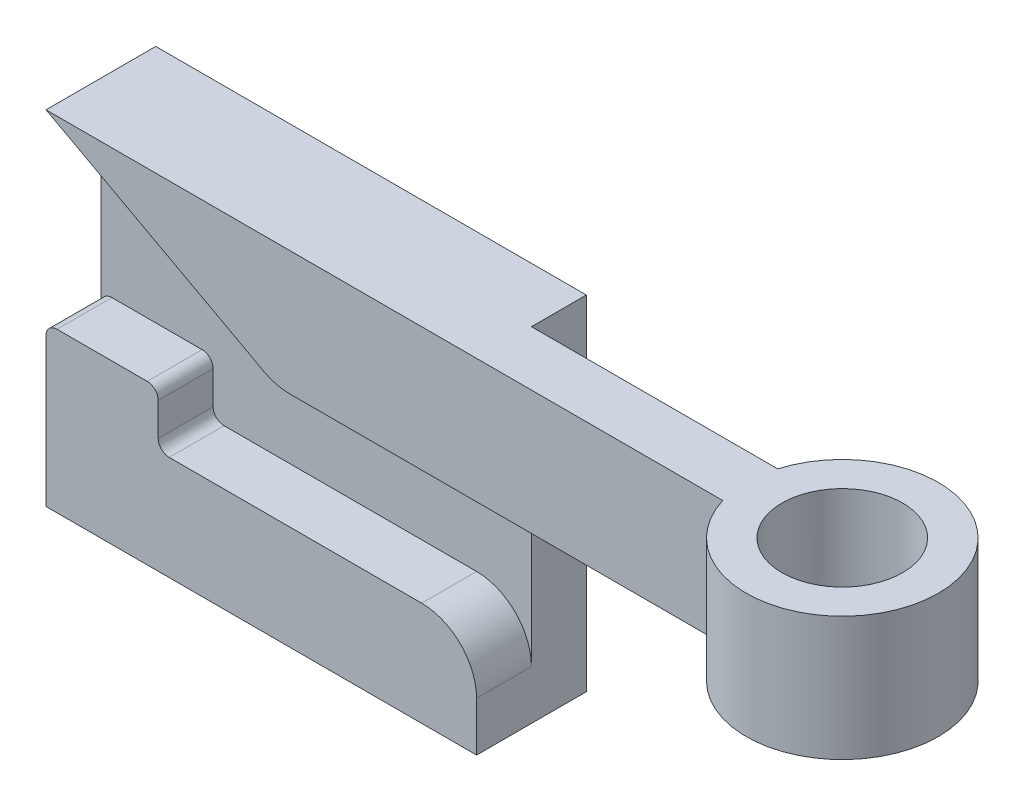
SolidWorks part; units mm, degrees
ref_plane "Front Plane" through (0, 0, 0) normal (0, 0, 1) x (1, 0, 0)
ref_plane "Top Plane" through (0, 0, 0) normal (0, 1, 0) x (1, 0, 0)
ref_plane "Right Plane" through (0, 0, 0) normal (1, 0, 0) x (0, 0, -1)
sketch "Sketch1" plane through (0, 0, 0) normal (0, 0, 1) x (1, 0, 0)
  line L1 (123.321, 27.8206) -> (41.9062, 27.8206)
  line L2 (41.9062, 27.8206) -> (0, 50.4466)
  line L3 (20.4481, 6.8206) -> (78.4559, 6.8206)
  line L6 (0, 16.8206) -> (20.4481, 16.8206)
  line L7 (20.4481, 6.8206) -> (20.4481, 16.8206)
  line L10 (0, 0) -> (0, -12.1545)
  line L11 (0, -12.1545) -> (78.4559, -12.1545)
  line L12 (78.4559, -12.1545) -> (78.4559, 6.8206)
  line L13 (0, 0) -> (0, 16.8206)
  line L14 (0, 50.4466) -> (123.321, 50.4466)
  line L17 (123.321, 50.4466) -> (123.321, 27.8206)
  point P3 (0, 67.3903)
  point P4 (50.4529, 26.6662)
  point P11 (0, 10.2755)
  point P14 (41.9062, 27.8206)
  point P16 (0, 50.4466)
  dimension "D1" = 21
  dimension "D2" = 10
extrude "Boss-Extrude1" add sketch "Sketch1" along normal blind 10
sketch "Sketch2" plane through (0, 0, 0) normal (0, 0, -1) x (-1, 0, 0)
  line L1 (0, 50.4466) -> (-78.4559, 50.4466)
  line L2 (0, 50.4466) -> (0, -12.1545)
  line L3 (0, -12.1545) -> (-78.4559, -12.1545)
  line L4 (-78.4559, 50.4466) -> (-78.4559, -12.1545)
extrude "Boss-Extrude2" add sketch "Sketch2" along normal blind 10
sketch "Sketch3" plane through (0, 50.4466, 0) normal (0, 1, 0) x (1, 0, 0)
  circle A0 centre (140.0915, -5) radius 17.5
  dimension "D2" = 35
extrude "Boss-Extrude3" add sketch "Sketch3" against normal up to surface (22.626 mm away) up to face at (81.782, 27.8206, 4)
sketch "Sketch4" plane through (0, 50.4466, 0) normal (0, 1, 0) x (1, 0, 0)
  arc A0 (123.321, -10) -> (123.321, 0) centre (140.0915, -5) ccw construction
  arc A1 (123.321, -10) -> (123.321, 0) centre (140.0915, -5) ccw construction
  circle A4 centre (140.0915, -5) radius 11
  dimension "D1" = 22
extrude "Cut-Extrude2" cut sketch "Sketch4" against normal up to next
fillet "Fillet1" radius 2 3 edges at (20.4481, 6.8206, 5) (0, 16.8206, 5) (20.4481, 16.8206, 5)
fillet "Fillet2" radius 10 2 edges at (78.4559, 6.8206, 5) (41.9062, 27.8206, 5)
